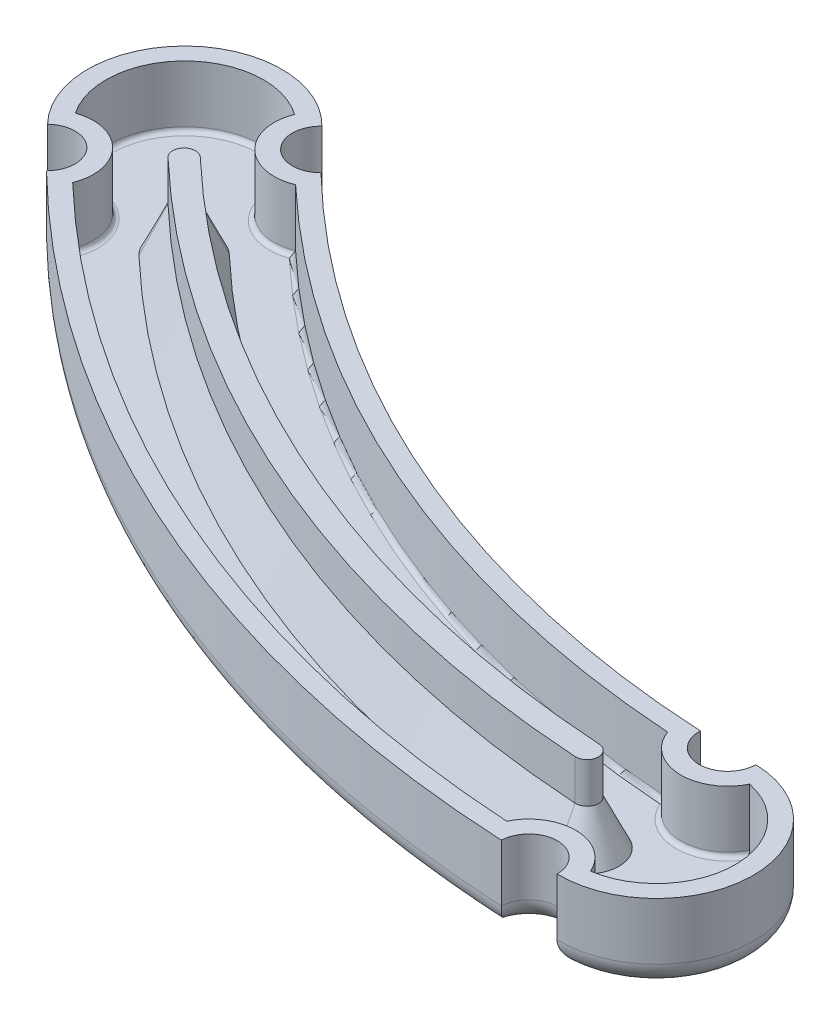
SolidWorks part; units mm, degrees
ref_plane "Front Plane" through (0, 0, 0) normal (0, 0, 1) x (1, 0, 0)
ref_plane "Top Plane" through (0, 0, 0) normal (0, 1, 0) x (1, 0, 0)
ref_plane "Right Plane" through (0, 0, 0) normal (1, 0, 0) x (0, 0, -1)
sketch "Sketch2" plane through (0, 0, 0) normal (0, 1, 0) x (1, 0, 0)
  line L0 (-71.3503, -82.2054) -> (-34958.9124, 35734.8019) construction
  line L1 (-70.1201, -59.1107) -> (-34995.8073, 35720.7213) construction
  line L2 (-39.7979, -107.5277) -> (49945.2079, -1331.9458) construction
  line L3 (31.7139, -92.3079) -> (50015.3873, -1369.9589) construction
  circle A0 centre (0, 0) radius 100 construction
  arc A1 (-0.2082, -108.4975) -> (0.2172, -91.5028) centre (0, -100) ccw
  arc A2 (-67.2386, -62.0626) -> (-79.4101, -73.9309) centre (-73.3212, -68) ccw
  arc A3 (-63.7464, -65.6403) -> (-4.7807, -91.375) centre (0, 0) ccw
  arc A4 (-75.9216, -77.5123) -> (-5.2063, -108.375) centre (0, 0) ccw
  arc A5 (-67.2386, -62.0626) -> (-63.7464, -65.6403) centre (-65.5159, -63.8743) ccw
  arc A6 (-75.9216, -77.5123) -> (-79.4101, -73.9309) centre (-77.6873, -75.7425) ccw
  arc A7 (-4.7807, -91.375) -> (0.2172, -91.5028) centre (-2.2826, -91.4715) ccw
  arc A8 (-0.2082, -108.4975) -> (-5.2063, -108.375) centre (-2.708, -108.4662) ccw
  dimension "D1" = 200
  dimension "D3" = 17
  dimension "D4" = 5
  dimension "D2" = 80
extrude "Boss-Extrude1" add sketch "Sketch2" along normal blind 7
fillet "Fillet1" radius 2 8 edges at (8.4973, 0, 100.2127) (-2.3465, 0, 93.9707) (-36.6, 0, 83.8611) (-67.3049, 0, 65.6206) (-79.2553, 0, 61.9143) (-75.8965, 0, 73.9981) (-43.4, 0, 99.4419) (-2.6467, 0, 105.967)
shell "Shell1" thickness 1.6 removed face at (-37.3691, 7, 85.6233)
sketch "Sketch3" plane through (0, 1.6, 0) normal (0, 1, 0) x (1, 0, 0)
  line L0 (-73.8794, -77.2622) -> (-63.9482, -67.6627) construction
  line L1 (-6.1264, -92.8982) -> (-6.4116, -106.7075) construction
  arc A0 (-68.9138, -72.4625) -> (-6.269, -99.8029) centre (0, 0) ccw construction
  arc A1 (-73.8794, -77.2622) -> (-6.4116, -106.7075) centre (0, 0) ccw construction
  arc A2 (-6.4116, -106.7075) -> (-4.8107, -104.9465) centre (-2.708, -108.4662) ccw construction
  arc A3 (-69.6029, -73.1871) -> (-6.3317, -100.8009) centre (0, 0) ccw
  arc A4 (-68.2246, -71.7378) -> (-6.2063, -98.8048) centre (0, 0) ccw
  arc A5 (-69.6029, -73.1871) -> (-68.2246, -71.7378) centre (-68.9138, -72.4625) cw
  arc A6 (-6.3317, -100.8009) -> (-6.2063, -98.8048) centre (-6.269, -99.8029) ccw
  point P16 (-6.269, -99.8029)
  point P24 (0, 0)
  dimension "D1" = 1
  dimension "D2" = 1
extrude "Boss-Extrude2" add sketch "Sketch3" along normal offset from surface (7.4 mm away) 2 up to face at (-37.4353, 7, 85.775) offset beyond the face yes
chamfer "Chamfer2" distance 1.8 angle 65 4 edges at (-39.5998, 1.6, 90.7346) (-69.6384, 1.6, 71.7733) (-5.271, 1.6, 99.8656) (-40.3998, 1.6, 92.5676) first distance on face at (-37.4529, 1.6, 85.8155)
